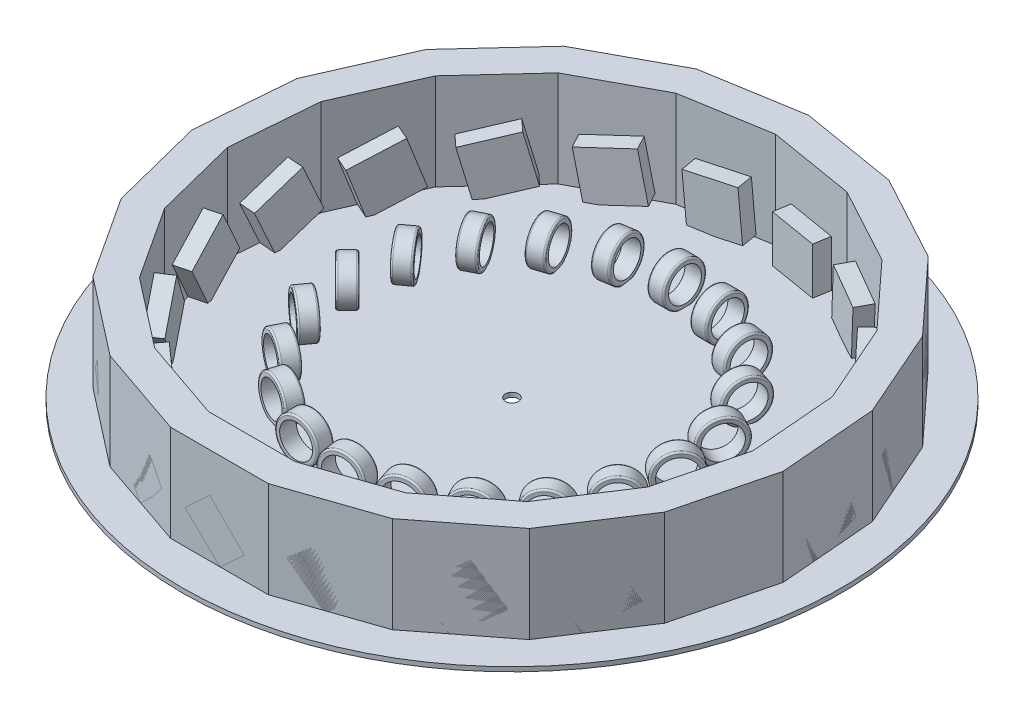
SolidWorks part; units mm, degrees
ref_plane "Front Plane" through (0, 0, 0) normal (0, 0, 1) x (1, 0, 0)
ref_plane "Top Plane" through (0, 0, 0) normal (0, 1, 0) x (1, 0, 0)
ref_plane "Right Plane" through (0, 0, 0) normal (1, 0, 0) x (0, 0, -1)
sketch "Sketch1" plane through (0, 0, 0) normal (0, 1, 0) x (1, 0, 0)
  circle A0 centre (0, 0) radius 100
  circle A1 centre (0, 0) radius 2
  dimension "D1" = 200
  dimension "D2" = 4
extrude "Base Platter" add sketch "Sketch1" along normal blind 0.75
sketch "Sketch3" plane through (0, 0.75, 0) normal (0, 1, 0) x (1, 0, 0)
  line L1 (0, 90) -> (-29.223, 85.1236)
  line L2 (-29.223, 85.1236) -> (-55.2791, 71.0226)
  line L3 (-55.2791, 71.0226) -> (-75.345, 49.2253)
  line L4 (-75.345, 49.2253) -> (-87.246, 22.0937)
  line L5 (-87.246, 22.0937) -> (-89.6926, -7.4321)
  line L6 (-89.6926, -7.4321) -> (-82.4196, -36.1526)
  line L7 (-82.4196, -36.1526) -> (-66.2152, -60.9553)
  line L8 (-66.2152, -60.9553) -> (-42.8353, -79.1526)
  line L9 (-42.8353, -79.1526) -> (-14.8135, -88.7725)
  line L10 (-14.8135, -88.7725) -> (14.8135, -88.7725)
  line L11 (14.8135, -88.7725) -> (42.8353, -79.1526)
  line L12 (42.8353, -79.1526) -> (66.2152, -60.9553)
  line L13 (66.2152, -60.9553) -> (82.4196, -36.1526)
  line L14 (82.4196, -36.1526) -> (89.6926, -7.4321)
  line L15 (89.6926, -7.4321) -> (87.246, 22.0937)
  line L16 (87.246, 22.0937) -> (75.345, 49.2253)
  line L17 (75.345, 49.2253) -> (55.2791, 71.0226)
  line L18 (55.2791, 71.0226) -> (29.223, 85.1236)
  line L19 (29.223, 85.1236) -> (0, 90)
  line L20 (0, 80) -> (-25.976, 75.6654)
  line L21 (-25.976, 75.6654) -> (-49.137, 63.1312)
  line L22 (-49.137, 63.1312) -> (-66.9733, 43.7559)
  line L23 (-66.9733, 43.7559) -> (-77.552, 19.6388)
  line L24 (-77.552, 19.6388) -> (-79.7268, -6.6063)
  line L25 (-79.7268, -6.6063) -> (-73.2619, -32.1356)
  line L26 (-73.2619, -32.1356) -> (-58.8579, -54.1825)
  line L27 (-58.8579, -54.1825) -> (-38.0758, -70.3579)
  line L28 (-38.0758, -70.3579) -> (-13.1676, -78.9089)
  line L29 (-13.1676, -78.9089) -> (13.1676, -78.9089)
  line L30 (13.1676, -78.9089) -> (38.0758, -70.3579)
  line L31 (38.0758, -70.3579) -> (58.8579, -54.1825)
  line L32 (58.8579, -54.1825) -> (73.2619, -32.1356)
  line L33 (73.2619, -32.1356) -> (79.7268, -6.6063)
  line L34 (79.7268, -6.6063) -> (77.552, 19.6388)
  line L35 (77.552, 19.6388) -> (66.9733, 43.7559)
  line L36 (66.9733, 43.7559) -> (49.137, 63.1312)
  line L37 (49.137, 63.1312) -> (25.976, 75.6654)
  line L38 (25.976, 75.6654) -> (0, 80)
  circle A0 centre (0, 0) radius 90 construction
  circle A1 centre (0, 0) radius 80 construction
  circle A2 centre (0, 0) radius 88.7725 construction
  circle A3 centre (0, 0) radius 78.9089 construction
  dimension "D1" = 180
  dimension "D2" = 160
extrude "Cube Face Reference" add sketch "Sketch3" along normal blind 29.8 separate body
sketch "Sketch4" plane through (14.6115, 0, -87.5618) normal (0.1646, 0, -0.9864) x (-0.9864, 0, -0.1646)
  line L0 (0, 0.75) -> (0, 30.55) construction
  line L1 (100, 0.75) -> (-100, 0.75) construction
  line L2 (-14.8135, 30.55) -> (14.8135, 30.55) construction
  line L3 (-14.8135, 0.75) -> (14.8135, 0.75) construction
  line L4 (-7.4075, 0.75) -> (7.4075, 0.75)
  line L5 (-7.4075, 0.75) -> (-7.4075, 15.57)
  line L6 (-7.4075, 15.57) -> (7.4075, 15.57)
  line L7 (7.4075, 0.75) -> (7.4075, 15.57)
  point P12 (0, 15.57)
  dimension "D1" = 14.815
  dimension "D2" = 14.82
extrude "First Cube" add sketch "Sketch4" against normal blind 14.82 separate body
sketch "Sketch5" plane through (42.251, 0, -78.0731) normal (0.4759, 0, -0.8795) x (-0.8795, 0, -0.4759)
  line L0 (-6.7728, 0.75) -> (7.9966, 1.9738)
  line L1 (-14.8135, 0.75) -> (14.8135, 0.75) construction
  line L2 (7.9966, 1.9738) -> (6.7728, 16.7432)
  line L3 (6.7728, 16.7432) -> (-7.9966, 15.5194)
  line L4 (-7.9966, 15.5194) -> (-6.7728, 0.75)
  line L5 (6.7728, 16.7432) -> (-6.7728, 0.75) construction
  line L6 (7.9966, 1.9738) -> (-7.9966, 15.5194) construction
  line L7 (100, 0.75) -> (-100, 0.75) construction
  line L8 (-14.8135, 30.55) -> (14.8135, 30.55) construction
  point P11 (0, 30.55)
  point P12 (0, 8.7466)
  dimension "D1" = 14.82
  dimension "D2" = 14.82
  dimension "D3" = 4.737
extrude "Boss-Extrude6" add sketch "Sketch5" against normal blind 14.82 separate body
sketch "Sketch6" plane through (65.3121, 0, -60.124) normal (0.7357, 0, -0.6773) x (-0.6773, 0, -0.7357)
  line L0 (-6.0893, 0.75) -> (-8.5286, 15.3679)
  line L1 (-14.8135, 0.75) -> (14.8135, 0.75) construction
  line L2 (-8.5286, 15.3679) -> (6.0893, 17.8072)
  line L3 (6.0893, 17.8072) -> (8.5286, 3.1893)
  line L4 (8.5286, 3.1893) -> (-6.0893, 0.75)
  line L5 (6.0893, 17.8072) -> (-6.0893, 0.75) construction
  line L6 (-8.5286, 15.3679) -> (8.5286, 3.1893) construction
  point P4 (0, 9.2786)
  dimension "D1" = 14.82
  dimension "D2" = 14.82
  dimension "D3" = 9.474
extrude "Boss-Extrude7" add sketch "Sketch6" against normal blind 14.82 separate body
sketch "Sketch7" plane through (81.2955, 0, -35.6595) normal (0.9158, 0, -0.4017) x (-0.4017, 0, -0.9158)
  line L0 (-5.3642, 0.75) -> (-9.0023, 15.1165)
  line L2 (-9.0023, 15.1165) -> (5.3642, 18.7546)
  line L3 (5.3642, 18.7546) -> (9.0023, 4.3881)
  line L4 (9.0023, 4.3881) -> (-5.3642, 0.75)
  line L5 (5.3642, 18.7546) -> (-5.3642, 0.75) construction
  line L6 (9.0023, 4.3881) -> (-9.0023, 15.1165) construction
  line L7 (100, 0.75) -> (-100, 0.75) construction
  line L8 (-14.8135, 0.75) -> (14.8135, 0.75) construction
  point P4 (0, 9.7523)
  dimension "D1" = 14.82
  dimension "D2" = 14.82
  dimension "D3" = 14.211
extrude "Boss-Extrude9" add sketch "Sketch7" against normal blind 14.82 separate body
sketch "Sketch8" plane through (88.4693, 0, -7.3308) normal (0.9966, 0, -0.0826) x (-0.0826, 0, -0.9966)
  line L0 (-4.6025, 0.75) -> (-9.4145, 14.767)
  line L2 (-9.4145, 14.767) -> (4.6025, 19.5791)
  line L3 (4.6025, 19.5791) -> (9.4145, 5.562)
  line L4 (9.4145, 5.562) -> (-4.6025, 0.75)
  line L5 (-14.8135, 0.75) -> (14.8135, 0.75) construction
  line L6 (-4.6025, 0.75) -> (4.6025, 19.5791) construction
  line L7 (9.4145, 5.562) -> (-9.4145, 14.767) construction
  line L8 (-14.8135, 30.55) -> (14.8135, 30.55) construction
  point P8 (0, 30.55)
  point P9 (0, 10.1645)
  dimension "D1" = 14.82
  dimension "D2" = 14.82
  dimension "D3" = 18.947
extrude "Boss-Extrude10" add sketch "Sketch8" against normal blind 14.82 separate body
sketch "Sketch9" plane through (86.0561, 0, 21.7924) normal (0.9694, 0, 0.2455) x (0.2455, 0, -0.9694)
  line L0 (-3.8093, 0.75) -> (-9.7624, 14.3218)
  line L1 (-14.8135, 0.75) -> (14.8135, 0.75) construction
  line L2 (-9.7624, 14.3218) -> (3.8093, 20.2749)
  line L3 (3.8093, 20.2749) -> (9.7624, 6.7031)
  line L4 (9.7624, 6.7031) -> (-3.8093, 0.75)
  line L5 (-3.8093, 0.75) -> (3.8093, 20.2749)
  line L6 (9.7624, 6.7031) -> (-9.7624, 14.3218)
  point P4 (0, 10.5124)
  dimension "D1" = 14.82
  dimension "D2" = 14.82
  dimension "D3" = 23.684
extrude "Boss-Extrude11" add sketch "Sketch9" against normal blind 14.82 separate body contours L6 L5 L2 | L6 L3 L5 | L4 L6 L5 | L5 L6 L0 region at (86.5432, 5.9885, 19.8687) region at (84.9455, 8.5281, 26.1779) region at (85.569, 15.0364, 23.716) region at (87.1667, 12.4968, 17.4069)
sketch "Sketch10" plane through (74.3174, 0, 48.554) normal (0.8372, 0, 0.5469) x (0.5469, 0, -0.8372)
  line L0 (-2.9901, 0.75) -> (-10.0437, 13.7838)
  line L1 (-14.8135, 0.75) -> (14.8135, 0.75) construction
  line L2 (-10.0437, 13.7838) -> (2.9901, 20.8373)
  line L3 (2.9901, 20.8373) -> (10.0437, 7.8035)
  line L4 (10.0437, 7.8035) -> (-2.9901, 0.75)
  line L5 (-2.9901, 0.75) -> (2.9901, 20.8373) construction
  line L6 (10.0437, 7.8035) -> (-10.0437, 13.7838) construction
  point P4 (0, 0.75)
  point P7 (0, 10.7937)
  dimension "D1" = 14.82
  dimension "D2" = 14.82
  dimension "D3" = 28.421
extrude "Boss-Extrude12" add sketch "Sketch10" against normal blind 14.82 separate body
sketch "Sketch11" plane through (54.5252, 0, 70.054) normal (0.6142, 0, 0.7891) x (0.7891, 0, -0.6142)
  line L0 (-2.1505, 0.75) -> (-10.2563, 13.1568)
  line L1 (-14.8135, 0.75) -> (14.8135, 0.75) construction
  line L2 (-10.2563, 13.1568) -> (2.1505, 21.2626)
  line L3 (2.1505, 21.2626) -> (10.2563, 8.8558)
  line L4 (10.2563, 8.8558) -> (-2.1505, 0.75)
  line L5 (2.1505, 21.2626) -> (-2.1505, 0.75) construction
  line L6 (10.2563, 8.8558) -> (-10.2563, 13.1568) construction
  line L7 (-14.8135, 30.55) -> (14.8135, 30.55) construction
  line L8 (100, 0.75) -> (-100, 0.75) construction
  point P8 (0, 30.55)
  point P9 (0, 11.0063)
  dimension "D1" = 14.82
  dimension "D2" = 14.82
  dimension "D3" = 33.158
extrude "Boss-Extrude14" add sketch "Sketch11" against normal blind 14.82 separate body
sketch "Sketch12" plane through (28.8244, 0, 83.9626) normal (0.3247, 0, 0.9458) x (0.9458, 0, -0.3247)
  line L0 (-1.2962, 0.75) -> (-10.3988, 12.4451)
  line L1 (100, 0.75) -> (-100, 0.75) construction
  line L2 (-10.3988, 12.4451) -> (1.2962, 21.5477)
  line L3 (1.2962, 21.5477) -> (10.3988, 9.8526)
  line L4 (10.3988, 9.8526) -> (-1.2962, 0.75)
  line L5 (1.2962, 21.5477) -> (-1.2962, 0.75) construction
  line L6 (-10.3988, 12.4451) -> (10.3988, 9.8526) construction
  line L7 (-14.8135, 30.55) -> (14.8135, 30.55) construction
  line L8 (-14.8135, 0.75) -> (14.8135, 0.75) construction
  point P8 (0, 30.55)
  point P9 (0, 11.1488)
  dimension "D1" = 14.82
  dimension "D2" = 14.82
  dimension "D3" = 37.895
extrude "Boss-Extrude15" add sketch "Sketch12" against normal blind 14.82 separate body
sketch "Sketch13" plane through (0, 0, 88.7725) normal (0, 0, 1) x (1, 0, 0)
  line L0 (-0.4331, 0.75) -> (-10.4704, 11.6534)
  line L1 (-14.8135, 0.75) -> (14.8135, 0.75) construction
  line L2 (-10.4704, 11.6534) -> (0.4331, 21.6907)
  line L3 (0.4331, 21.6907) -> (10.4704, 10.7873)
  line L4 (10.4704, 10.7873) -> (-0.4331, 0.75)
  line L5 (0.4331, 21.6907) -> (-0.4331, 0.75) construction
  line L6 (-10.4704, 11.6534) -> (10.4704, 10.7873) construction
  line L7 (100, 0.75) -> (-100, 0.75) construction
  point P8 (0, 0.75)
  point P9 (0, 11.2204)
  dimension "D1" = 14.82
  dimension "D2" = 14.82
  dimension "D3" = 42.632
extrude "Boss-Extrude16" add sketch "Sketch13" against normal blind 14.82 separate body
sketch "Sketch14" plane through (-28.8244, 0, 83.9626) normal (-0.3247, 0, 0.9458) x (0.9458, 0, 0.3247)
  line L0 (0.4331, 0.75) -> (-10.4704, 10.7873)
  line L1 (100, 0.75) -> (-100, 0.75) construction
  line L2 (-10.4704, 10.7873) -> (-0.4331, 21.6907)
  line L3 (-0.4331, 21.6907) -> (10.4704, 11.6534)
  line L4 (10.4704, 11.6534) -> (0.4331, 0.75)
  line L5 (0.4331, 0.75) -> (-0.4331, 21.6907) construction
  line L6 (-10.4704, 10.7873) -> (10.4704, 11.6534) construction
  line L7 (-14.8135, 0.75) -> (14.8135, 0.75) construction
  point P4 (0, 11.2204)
  dimension "D1" = 14.82
  dimension "D2" = 14.82
  dimension "D3" = 47.368
extrude "Boss-Extrude18" add sketch "Sketch14" against normal blind 14.82 separate body
sketch "Sketch15" plane through (-54.5252, 0, 70.054) normal (-0.6142, 0, 0.7891) x (0.7891, 0, 0.6142)
  line L0 (1.2962, 0.75) -> (-10.3988, 9.8526)
  line L1 (-14.8135, 0.75) -> (14.8135, 0.75) construction
  line L2 (-10.3988, 9.8526) -> (-1.2962, 21.5477)
  line L3 (-1.2962, 21.5477) -> (10.3988, 12.4451)
  line L4 (10.3988, 12.4451) -> (1.2962, 0.75)
  line L5 (1.2962, 0.75) -> (-1.2962, 21.5477) construction
  line L6 (10.3988, 12.4451) -> (-10.3988, 9.8526) construction
  line L7 (-14.8135, 30.55) -> (14.8135, 30.55) construction
  line L8 (100, 0.75) -> (-100, 0.75) construction
  point P8 (0, 30.55)
  point P9 (0, 11.1488)
  dimension "D1" = 14.82
  dimension "D2" = 14.82
  dimension "D3" = 52.105
extrude "Boss-Extrude19" add sketch "Sketch15" against normal blind 14.82 separate body
sketch "Sketch16" plane through (-74.3174, 0, 48.554) normal (-0.8372, 0, 0.5469) x (0.5469, 0, 0.8372)
  line L0 (2.1505, 0.75) -> (-10.2563, 8.8558)
  line L1 (-14.8135, 0.75) -> (14.8135, 0.75) construction
  line L2 (-10.2563, 8.8558) -> (-2.1505, 21.2626)
  line L3 (-2.1505, 21.2626) -> (10.2563, 13.1568)
  line L4 (10.2563, 13.1568) -> (2.1505, 0.75)
  line L5 (2.1505, 0.75) -> (-2.1505, 21.2626) construction
  line L6 (10.2563, 13.1568) -> (-10.2563, 8.8558) construction
  line L7 (-14.8135, 30.55) -> (14.8135, 30.55) construction
  point P8 (0, 30.55)
  point P9 (0, 11.0063)
  dimension "D1" = 14.82
  dimension "D2" = 14.82
  dimension "D3" = 56.842
extrude "Boss-Extrude20" add sketch "Sketch16" against normal blind 14.82 separate body
sketch "Sketch17" plane through (-86.0561, 0, 21.7924) normal (-0.9694, 0, 0.2455) x (0.2455, 0, 0.9694)
  line L0 (2.9901, 0.75) -> (-10.0437, 7.8035)
  line L1 (100, 0.75) -> (-100, 0.75) construction
  line L2 (-10.0437, 7.8035) -> (-2.9901, 20.8373)
  line L3 (-2.9901, 20.8373) -> (10.0437, 13.7838)
  line L4 (10.0437, 13.7838) -> (2.9901, 0.75)
  line L5 (2.9901, 0.75) -> (-2.9901, 20.8373) construction
  line L6 (10.0437, 13.7838) -> (-10.0437, 7.8035) construction
  line L7 (-14.8135, 30.55) -> (14.8135, 30.55) construction
  line L8 (-14.8135, 0.75) -> (14.8135, 0.75) construction
  point P8 (0, 30.55)
  point P9 (0, 10.7937)
  dimension "D1" = 14.82
  dimension "D2" = 14.82
  dimension "D3" = 14.82
  dimension "D4" = 61.579
extrude "Boss-Extrude21" add sketch "Sketch17" against normal blind 14.82 separate body
sketch "Sketch18" plane through (-88.4693, 0, -7.3308) normal (-0.9966, 0, -0.0826) x (-0.0826, 0, 0.9966)
  line L0 (3.8093, 0.75) -> (-9.7624, 6.7031)
  line L1 (100, 0.75) -> (-100, 0.75) construction
  line L2 (-9.7624, 6.7031) -> (-3.8093, 20.2749)
  line L3 (-3.8093, 20.2749) -> (9.7624, 14.3218)
  line L4 (9.7624, 14.3218) -> (3.8093, 0.75)
  line L5 (-3.8093, 20.2749) -> (3.8093, 0.75) construction
  line L6 (9.7624, 14.3218) -> (-9.7624, 6.7031) construction
  line L7 (-14.8135, 30.55) -> (14.8135, 30.55) construction
  line L8 (-14.8135, 0.75) -> (14.8135, 0.75) construction
  point P8 (0, 30.55)
  point P9 (0, 10.5124)
  dimension "D1" = 14.82
  dimension "D2" = 14.82
  dimension "D3" = 66.316
extrude "Boss-Extrude23" add sketch "Sketch18" against normal blind 14.82 separate body
sketch "Sketch19" plane through (-81.2955, 0, -35.6595) normal (-0.9158, 0, -0.4017) x (-0.4017, 0, 0.9158)
  line L0 (4.6025, 0.75) -> (-9.4145, 5.562)
  line L1 (-14.8135, 0.75) -> (14.8135, 0.75) construction
  line L2 (-9.4145, 5.562) -> (-4.6025, 19.5791)
  line L3 (-4.6025, 19.5791) -> (9.4145, 14.767)
  line L4 (9.4145, 14.767) -> (4.6025, 0.75)
  line L5 (4.6025, 0.75) -> (-4.6025, 19.5791) construction
  line L6 (9.4145, 14.767) -> (-9.4145, 5.562) construction
  line L7 (-14.8135, 30.55) -> (14.8135, 30.55) construction
  point P8 (0, 30.55)
  point P9 (0, 10.1645)
  dimension "D1" = 14.82
  dimension "D2" = 14.82
  dimension "D3" = 71.053
extrude "Boss-Extrude24" add sketch "Sketch19" against normal blind 14.82 separate body
sketch "Sketch20" plane through (-65.3121, 0, -60.124) normal (-0.7357, 0, -0.6773) x (-0.6773, 0, 0.7357)
  line L0 (5.3642, 0.75) -> (-9.0023, 4.3881)
  line L1 (100, 0.75) -> (-100, 0.75) construction
  line L2 (-9.0023, 4.3881) -> (-5.3642, 18.7546)
  line L3 (-5.3642, 18.7546) -> (9.0023, 15.1165)
  line L4 (9.0023, 15.1165) -> (5.3642, 0.75)
  line L5 (-5.3642, 18.7546) -> (5.3642, 0.75) construction
  line L6 (9.0023, 15.1165) -> (-9.0023, 4.3881) construction
  line L7 (-14.8135, 30.55) -> (14.8135, 30.55) construction
  point P8 (0, 30.55)
  point P9 (0, 9.7523)
  dimension "D1" = 14.82
  dimension "D2" = 14.82
  dimension "D3" = 75.789
extrude "Boss-Extrude25" add sketch "Sketch20" against normal blind 14.82 separate body
sketch "Sketch21" plane through (-42.251, 0, -78.0731) normal (-0.4759, 0, -0.8795) x (-0.8795, 0, 0.4759)
  line L0 (6.0893, 0.75) -> (-8.5286, 3.1893)
  line L1 (-14.8135, 0.75) -> (14.8135, 0.75) construction
  line L2 (-8.5286, 3.1893) -> (-6.0893, 17.8072)
  line L3 (-6.0893, 17.8072) -> (8.5286, 15.3679)
  line L4 (8.5286, 15.3679) -> (6.0893, 0.75)
  line L5 (6.0893, 0.75) -> (-6.0893, 17.8072) construction
  line L6 (8.5286, 15.3679) -> (-8.5286, 3.1893) construction
  line L7 (-14.8135, 30.55) -> (14.8135, 30.55) construction
  point P8 (0, 30.55)
  point P9 (0, 9.2786)
  dimension "D1" = 14.82
  dimension "D2" = 14.82
  dimension "D3" = 80.526
extrude "Boss-Extrude26" add sketch "Sketch21" against normal blind 14.82 separate body
sketch "Sketch22" plane through (-14.6115, 0, -87.5618) normal (-0.1646, 0, -0.9864) x (-0.9864, 0, 0.1646)
  line L0 (6.7728, 0.75) -> (-7.9966, 1.9738)
  line L1 (-14.8135, 0.75) -> (14.8135, 0.75) construction
  line L2 (-7.9966, 1.9738) -> (-6.7728, 16.7432)
  line L3 (-6.7728, 16.7432) -> (7.9966, 15.5194)
  line L4 (7.9966, 15.5194) -> (6.7728, 0.75)
  line L5 (6.7728, 0.75) -> (-6.7728, 16.7432) construction
  line L6 (-7.9966, 1.9738) -> (7.9966, 15.5194) construction
  line L7 (100, 0.75) -> (-100, 0.75) construction
  point P4 (0, 8.7466)
  dimension "D1" = 14.82
  dimension "D2" = 14.82
  dimension "D3" = 85.263
extrude "Boss-Extrude27" add sketch "Sketch22" against normal blind 14.82 separate body
sketch "Sketch23" plane through (0, 0.75, 0) normal (0, 1, 0) x (1, 0, 0)
  line L0 (0, 0) -> (0, 50) construction
  line L1 (0, 0) -> (15.4508, 47.5528) construction
  line L6 (0, 0) -> (29.3893, 40.4508) construction
  line L7 (0, 0) -> (40.4508, 29.3893) construction
  line L8 (0, 0) -> (47.5528, 15.4508) construction
  line L9 (0, 0) -> (50, 0) construction
  line L10 (0, 0) -> (47.5528, -15.4508) construction
  line L11 (0, 0) -> (40.4508, -29.3893) construction
  line L12 (0, 0) -> (29.3893, -40.4508) construction
  line L13 (0, 0) -> (15.4508, -47.5528) construction
  line L14 (0, 0) -> (0, -50) construction
  line L15 (0, 0) -> (-15.4508, -47.5528) construction
  line L16 (0, 0) -> (-29.3893, -40.4508) construction
  line L17 (0, 0) -> (-40.4508, -29.3893) construction
  line L18 (0, 0) -> (-47.5528, -15.4508) construction
  line L19 (0, 0) -> (-50, 0) construction
  line L20 (0, 0) -> (-47.5528, 15.4508) construction
  line L21 (0, 0) -> (-40.4508, 29.3893) construction
  line L22 (0, 0) -> (-29.3893, 40.4508) construction
  line L23 (0, 0) -> (-15.4508, 47.5528) construction
  line L24 (12.9508, 54.0528) -> (12.9508, 41.0528)
  line L25 (-2.5, 56.5) -> (2.5, 56.5)
  line L26 (-2.5, 56.5) -> (-2.5, 43.5)
  line L27 (-2.5, 43.5) -> (2.5, 43.5)
  line L28 (2.5, 56.5) -> (2.5, 43.5)
  line L29 (12.9508, 41.0528) -> (17.9508, 41.0528)
  line L30 (17.9508, 41.0528) -> (17.9508, 54.0528)
  line L31 (17.9508, 54.0528) -> (12.9508, 54.0528)
  line L32 (12.9508, 41.0528) -> (17.9508, 54.0528) construction
  line L33 (17.9508, 41.0528) -> (12.9508, 54.0528) construction
  line L34 (27.9369, 47.2619) -> (32.8753, 46.4797)
  line L35 (32.8753, 46.4797) -> (30.8417, 33.6398)
  line L36 (30.8417, 33.6398) -> (25.9032, 34.422)
  line L37 (25.9032, 34.422) -> (27.9369, 47.2619)
  line L38 (25.9032, 34.422) -> (32.8753, 46.4797) construction
  line L39 (30.8417, 33.6398) -> (27.9369, 47.2619) construction
  line L40 (40.0818, 36.3437) -> (36.0646, 23.9799)
  line L41 (36.0646, 23.9799) -> (40.8199, 22.4349)
  line L42 (40.8199, 22.4349) -> (44.8371, 34.7986)
  line L43 (44.8371, 34.7986) -> (40.0818, 36.3437)
  line L44 (40.8199, 22.4349) -> (40.0818, 36.3437) construction
  line L45 (44.8371, 34.7986) -> (36.0646, 23.9799) construction
  line L46 (48.2762, 22.3774) -> (42.3744, 10.7943)
  line L47 (42.3744, 10.7943) -> (46.8294, 8.5243)
  line L48 (46.8294, 8.5243) -> (52.7313, 20.1074)
  line L49 (52.7313, 20.1074) -> (48.2762, 22.3774)
  line L50 (46.8294, 8.5243) -> (48.2762, 22.3774) construction
  line L51 (52.7313, 20.1074) -> (42.3744, 10.7943) construction
  line L52 (51.7981, 6.7281) -> (44.1569, -3.7891)
  line L53 (44.1569, -3.7891) -> (48.2019, -6.7281)
  line L54 (48.2019, -6.7281) -> (55.8431, 3.7891)
  line L55 (55.8431, 3.7891) -> (51.7981, 6.7281)
  line L56 (48.2019, -6.7281) -> (51.7981, 6.7281) construction
  line L57 (55.8431, 3.7891) -> (44.1569, -3.7891) construction
  line L58 (50.3813, -9.0869) -> (41.1889, -18.2793)
  line L59 (41.1889, -18.2793) -> (44.7244, -21.8148)
  line L60 (44.7244, -21.8148) -> (53.9168, -12.6224)
  line L61 (53.9168, -12.6224) -> (50.3813, -9.0869)
  line L62 (44.7244, -21.8148) -> (50.3813, -9.0869) construction
  line L63 (53.9168, -12.6224) -> (41.1889, -18.2793) construction
  line L64 (44.24, -23.5461) -> (33.7228, -31.1873)
  line L65 (33.7228, -31.1873) -> (36.6617, -35.2324)
  line L66 (36.6617, -35.2324) -> (47.1789, -27.5912)
  line L67 (47.1789, -27.5912) -> (44.24, -23.5461)
  line L68 (36.6617, -35.2324) -> (44.24, -23.5461) construction
  line L69 (47.1789, -27.5912) -> (33.7228, -31.1873) construction
  line L70 (24.7327, -45.6293) -> (36.3158, -39.7274)
  line L71 (36.3158, -39.7274) -> (34.0458, -35.2724)
  line L72 (34.0458, -35.2724) -> (22.4627, -41.1743)
  line L73 (22.4627, -41.1743) -> (24.7327, -45.6293)
  line L74 (34.0458, -35.2724) -> (24.7327, -45.6293) construction
  line L75 (22.4627, -41.1743) -> (36.3158, -39.7274) construction
  line L76 (10.0415, -51.9391) -> (22.4053, -47.9219)
  line L77 (22.4053, -47.9219) -> (20.8602, -43.1666)
  line L78 (20.8602, -43.1666) -> (8.4964, -47.1838)
  line L79 (8.4964, -47.1838) -> (10.0415, -51.9391)
  line L80 (20.8602, -43.1666) -> (10.0415, -51.9391) construction
  line L81 (8.4964, -47.1838) -> (22.4053, -47.9219) construction
  line L82 (-6.0289, -53.486) -> (6.8111, -51.4524)
  line L83 (6.8111, -51.4524) -> (6.0289, -46.514)
  line L84 (6.0289, -46.514) -> (-6.8111, -48.5476)
  line L85 (-6.8111, -48.5476) -> (-6.0289, -53.486)
  line L86 (6.0289, -46.514) -> (-6.0289, -53.486) construction
  line L87 (-6.8111, -48.5476) -> (6.8111, -51.4524) construction
  line L88 (-21.9508, -50.0528) -> (-8.9508, -50.0528)
  line L89 (-8.9508, -50.0528) -> (-8.9508, -45.0528)
  line L90 (-8.9508, -45.0528) -> (-21.9508, -45.0528)
  line L91 (-21.9508, -45.0528) -> (-21.9508, -50.0528)
  line L92 (-8.9508, -45.0528) -> (-21.9508, -50.0528) construction
  line L93 (-21.9508, -45.0528) -> (-8.9508, -50.0528) construction
  line L94 (-36.3437, -40.8199) -> (-23.9799, -44.8371)
  line L95 (-23.9799, -44.8371) -> (-22.4349, -40.0818)
  line L96 (-22.4349, -40.0818) -> (-34.7986, -36.0646)
  line L97 (-34.7986, -36.0646) -> (-36.3437, -40.8199)
  line L98 (-22.4349, -40.0818) -> (-36.3437, -40.8199) construction
  line L99 (-34.7986, -36.0646) -> (-23.9799, -44.8371) construction
  line L100 (-47.3774, -28.6658) -> (-35.7943, -34.5677)
  line L101 (-35.7943, -34.5677) -> (-33.5243, -30.1127)
  line L102 (-33.5243, -30.1127) -> (-45.1074, -24.2108)
  line L103 (-45.1074, -24.2108) -> (-47.3774, -28.6658)
  line L104 (-33.5243, -30.1127) -> (-47.3774, -28.6658) construction
  line L105 (-45.1074, -24.2108) -> (-35.7943, -34.5677) construction
  line L106 (-54.2809, -13.6528) -> (-43.7637, -21.294)
  line L107 (-43.7637, -21.294) -> (-40.8248, -17.2489)
  line L108 (-40.8248, -17.2489) -> (-51.342, -9.6077)
  line L109 (-51.342, -9.6077) -> (-54.2809, -13.6528)
  line L110 (-40.8248, -17.2489) -> (-54.2809, -13.6528) construction
  line L111 (-51.342, -9.6077) -> (-43.7637, -21.294) construction
  line L112 (-56.364, 2.8284) -> (-47.1716, -6.364)
  line L113 (-47.1716, -6.364) -> (-43.636, -2.8284)
  line L114 (-43.636, -2.8284) -> (-52.8284, 6.364)
  line L115 (-52.8284, 6.364) -> (-56.364, 2.8284)
  line L116 (-43.636, -2.8284) -> (-56.364, 2.8284) construction
  line L117 (-52.8284, 6.364) -> (-47.1716, -6.364) construction
  line L118 (-53.396, 19.24) -> (-45.7548, 8.7228)
  line L119 (-45.7548, 8.7228) -> (-41.7097, 11.6617)
  line L120 (-41.7097, 11.6617) -> (-49.3509, 22.1789)
  line L121 (-49.3509, 22.1789) -> (-53.396, 19.24)
  line L122 (-41.7097, 11.6617) -> (-53.396, 19.24) construction
  line L123 (-49.3509, 22.1789) -> (-45.7548, 8.7228) construction
  line L124 (-45.6293, 34.0458) -> (-39.7274, 22.4627)
  line L125 (-39.7274, 22.4627) -> (-35.2724, 24.7327)
  line L126 (-35.2724, 24.7327) -> (-41.1743, 36.3158)
  line L127 (-41.1743, 36.3158) -> (-45.6293, 34.0458)
  line L128 (-35.2724, 24.7327) -> (-45.6293, 34.0458) construction
  line L129 (-41.1743, 36.3158) -> (-39.7274, 22.4627) construction
  line L130 (-33.7755, 45.8602) -> (-29.7583, 33.4964)
  line L131 (-29.7583, 33.4964) -> (-25.003, 35.0415)
  line L132 (-25.003, 35.0415) -> (-29.0202, 47.4053)
  line L133 (-29.0202, 47.4053) -> (-33.7755, 45.8602)
  line L134 (-25.003, 35.0415) -> (-33.7755, 45.8602) construction
  line L135 (-29.0202, 47.4053) -> (-29.7583, 33.4964) construction
  line L136 (-18.9369, 53.5817) -> (-16.9032, 40.7418)
  line L137 (-16.9032, 40.7418) -> (-11.9648, 41.5239)
  line L138 (-11.9648, 41.5239) -> (-13.9985, 54.3639)
  line L139 (-13.9985, 54.3639) -> (-18.9369, 53.5817)
  line L140 (-11.9648, 41.5239) -> (-18.9369, 53.5817) construction
  line L141 (-13.9985, 54.3639) -> (-16.9032, 40.7418) construction
  point P25 (0, 0)
  point P27 (0, 56.5)
  point P28 (2.5, 50)
  point P31 (15.4508, 47.5528)
  point P36 (29.3893, 40.4508)
  point P47 (-47.5528, -15.4508)
  point P50 (-50, 0)
  point P51 (-47.5528, 15.4508)
  point P54 (-40.4508, 29.3893)
  point P57 (-29.3893, 40.4508)
  point P63 (-15.4508, 47.5528)
  point P69 (29.3893, -40.4508)
  point P140 (40.4508, 29.3893)
  point P141 (47.5528, 15.4508)
  point P142 (50, 0)
  point P144 (47.5528, -15.4508)
  point P146 (40.4508, -29.3893)
  point P149 (15.4508, -47.5528)
  point P151 (0, -50)
  point P153 (-15.4508, -47.5528)
  point P154 (-29.3893, -40.4508)
  point P155 (-40.4508, -29.3893)
  dimension "D1" = 50
  dimension "D2" = 20
  dimension "D3" = 5
  dimension "D4" = 13
  dimension "D5" = 5
  dimension "D6" = 13
  dimension "D7" = 18
  dimension "D8" = 5
  dimension "D9" = 13
  dimension "D10" = 27
  dimension "D11" = 5
  dimension "D12" = 13
  dimension "D13" = 36
  dimension "D14" = 5
  dimension "D15" = 13
  dimension "D16" = 45
  dimension "D17" = 5
  dimension "D18" = 13
  dimension "D19" = 54
  dimension "D20" = 5
  dimension "D21" = 13
  dimension "D22" = 63
  dimension "D23" = 5
  dimension "D24" = 13
  dimension "D25" = 72
  dimension "D26" = 5
  dimension "D27" = 13
  dimension "D28" = 81
  dimension "D29" = 5
  dimension "D30" = 13
  dimension "D31" = 90
  dimension "D32" = 5
  dimension "D33" = 13
  dimension "D34" = 99
  dimension "D35" = 5
  dimension "D36" = 13
  dimension "D37" = 108
  dimension "D38" = 5
  dimension "D39" = 13
  dimension "D40" = 108
  dimension "D41" = 5
  dimension "D42" = 13
  dimension "D43" = 117
  dimension "D44" = 5
  dimension "D45" = 13
  dimension "D46" = 126
  dimension "D47" = 5
  dimension "D48" = 13
  dimension "D49" = 135
  dimension "D50" = 5
  dimension "D51" = 13
  dimension "D52" = 144
  dimension "D53" = 5
  dimension "D54" = 13
  dimension "D55" = 153
  dimension "D56" = 5
  dimension "D57" = 13
  dimension "D58" = 162
  dimension "D59" = 5
  dimension "D60" = 13
  dimension "D61" = 171
extrude "Rings" add sketch "Sketch23" along normal blind 13 separate body
sketch "Sketch26" plane through (-5.2562, 0, 0.8325) normal (0.9877, 0, -0.1564) x (-0.1564, 0, -0.9877)
  line L0 (42.8844, 13.75) -> (55.8844, 13.75) construction
  line L1 (55.8844, 13.75) -> (55.8844, 0.75) construction
  line L3 (42.8844, 13.75) -> (55.8844, 13.75)
  line L4 (42.8844, 13.75) -> (42.8844, 0.75)
  line L5 (42.8844, 0.75) -> (55.8844, 0.75)
  line L6 (55.8844, 13.75) -> (55.8844, 0.75)
  circle A0 centre (49.3844, 7.25) radius 5
  circle A1 centre (49.3844, 7.25) radius 6.5
  point P5 (49.3844, 13.75)
  point P8 (55.8844, 7.25)
  line M2 (42.8844, 0.75) -> (55.8844, 0.75)
  line M3 (55.8844, 0.75) -> (55.8844, 13.75)
  line M4 (55.8844, 13.75) -> (42.8844, 13.75)
  line M5 (42.8844, 13.75) -> (42.8844, 0.75)
  dimension "D1" = 10
  dimension "D2" = 13
extrude "Cut-Extrude2" cut sketch "Sketch26" against normal up to surface (5 mm away) contours A0 | A1 L3 M5 | A1 L6 M4 | A1 L5 M3 | A1 L4 M2 region at (-12.1919, 12.2981, -42.958) region at (-13.7713, 12.2981, -52.9299) region at (-12.1919, 2.2019, -42.958) region at (-13.7713, 2.2019, -52.9299) region at (-12.9816, 7.25, -47.9439) up to face at (-17.9201, 7.25, -47.1617)
sketch "Sketch27" plane through (2.5, 0, 0) normal (1, 0, 0) x (0, 0, -1)
  line L0 (43.5, 13.75) -> (56.5, 13.75) construction
  line L1 (56.5, 13.75) -> (56.5, 0.75) construction
  line L3 (43.5, 13.75) -> (56.5, 13.75)
  line L4 (43.5, 13.75) -> (43.5, 0.75)
  line L5 (43.5, 0.75) -> (56.5, 0.75)
  line L6 (56.5, 13.75) -> (56.5, 0.75)
  circle A0 centre (50, 7.25) radius 5
  circle A1 centre (50, 7.25) radius 6.5
  point P4 (50, 13.75)
  point P7 (56.5, 7.25)
  line M2 (43.5, 0.75) -> (56.5, 0.75)
  line M3 (56.5, 0.75) -> (56.5, 13.75)
  line M4 (56.5, 13.75) -> (43.5, 13.75)
  line M5 (43.5, 13.75) -> (43.5, 0.75)
  dimension "D1" = 10
  dimension "D2" = 13
extrude "Cut-Extrude3" cut sketch "Sketch27" against normal up to surface (5 mm away) contours A0 | A1 L3 M5 | A1 L4 M2 | A1 L6 M4 | A1 L5 M3 region at (2.5, 12.2981, -44.9519) region at (2.5, 12.2981, -55.0481) region at (2.5, 2.2019, -44.9519) region at (2.5, 2.2019, -55.0481) region at (2.5, 7.25, -50) up to face at (-2.5, 7.25, -50)
sketch "Sketch28" plane through (17.9508, 0, 0) normal (1, 0, 0) x (0, 0, -1)
  line L0 (41.0528, 13.75) -> (54.0528, 13.75) construction
  line L1 (54.0528, 13.75) -> (54.0528, 0.75) construction
  line L3 (41.0528, 13.75) -> (54.0528, 13.75)
  line L4 (41.0528, 13.75) -> (41.0528, 0.75)
  line L5 (41.0528, 0.75) -> (54.0528, 0.75)
  line L6 (54.0528, 13.75) -> (54.0528, 0.75)
  circle A0 centre (47.5528, 7.25) radius 5
  circle A1 centre (47.5528, 7.25) radius 6.5
  point P4 (47.5528, 13.75)
  point P7 (54.0528, 7.25)
  line M2 (41.0528, 0.75) -> (54.0528, 0.75)
  line M3 (54.0528, 0.75) -> (54.0528, 13.75)
  line M4 (54.0528, 13.75) -> (41.0528, 13.75)
  line M5 (41.0528, 13.75) -> (41.0528, 0.75)
  dimension "D1" = 10
  dimension "D2" = 13
extrude "Cut-Extrude4" cut sketch "Sketch28" against normal up to surface (5 mm away) contours A1 L3 M5 | A1 L4 M2 | A0 | A1 L6 M4 | A1 L5 M3 region at (17.9508, 12.2981, -42.5047) region at (17.9508, 12.2981, -52.6009) region at (17.9508, 2.2019, -42.5047) region at (17.9508, 2.2019, -52.6009) region at (17.9508, 7.25, -47.5528) up to face at (12.9508, 7.25, -47.5528)
sketch "Sketch29" plane through (24.8893, 0, 3.9421) normal (0.9877, 0, 0.1564) x (0.1564, 0, -0.9877)
  line L0 (38.0503, 13.75) -> (51.0503, 13.75) construction
  line L1 (51.0503, 13.75) -> (51.0503, 0.75) construction
  line L3 (38.0503, 13.75) -> (51.0503, 13.75)
  line L4 (38.0503, 13.75) -> (38.0503, 0.75)
  line L5 (38.0503, 0.75) -> (51.0503, 0.75)
  line L6 (51.0503, 13.75) -> (51.0503, 0.75)
  circle A0 centre (44.5503, 7.25) radius 5
  circle A1 centre (44.5503, 7.25) radius 6.5
  point P4 (44.5503, 13.75)
  point P7 (51.0503, 7.25)
  line M2 (38.0503, 0.75) -> (51.0503, 0.75)
  line M3 (51.0503, 0.75) -> (51.0503, 13.75)
  line M4 (51.0503, 13.75) -> (38.0503, 13.75)
  line M5 (38.0503, 13.75) -> (38.0503, 0.75)
  dimension "D1" = 10
  dimension "D2" = 13
extrude "Cut-Extrude5" cut sketch "Sketch29" against normal up to surface (5 mm away) contours A0 | A1 L3 M5 | A1 L4 M2 | A1 L5 M3 | A1 L6 M4 region at (31.0688, 12.2981, -35.0738) region at (32.6482, 12.2981, -45.0457) region at (31.0688, 2.2019, -35.0738) region at (32.6482, 2.2019, -45.0457) region at (31.8585, 7.25, -40.0598) up to face at (26.92, 7.25, -40.8419)
sketch "Sketch30" plane through (30.3285, 0, 9.8543) normal (0.9511, 0, 0.309) x (0.309, 0, -0.9511)
  line L0 (33.9508, 13.75) -> (46.9508, 13.75) construction
  line L1 (46.9508, 13.75) -> (46.9508, 0.75) construction
  line L3 (33.9508, 13.75) -> (46.9508, 13.75)
  line L4 (33.9508, 13.75) -> (33.9508, 0.75)
  line L5 (33.9508, 0.75) -> (46.9508, 0.75)
  line L6 (46.9508, 13.75) -> (46.9508, 0.75)
  circle A0 centre (40.4508, 7.25) radius 5
  circle A1 centre (40.4508, 7.25) radius 6.5
  point P4 (40.4508, 13.75)
  point P7 (46.9508, 7.25)
  line M2 (33.9508, 0.75) -> (46.9508, 0.75)
  line M3 (46.9508, 0.75) -> (46.9508, 13.75)
  line M4 (46.9508, 13.75) -> (33.9508, 13.75)
  line M5 (33.9508, 13.75) -> (33.9508, 0.75)
  dimension "D1" = 10
  dimension "D2" = 13
extrude "Cut-Extrude6" cut sketch "Sketch30" against normal up to surface (5 mm away) contours A1 L3 M5 | A1 L4 M2 | A0 | A1 L6 M4 | A1 L5 M3 region at (41.2685, 12.2981, -23.8157) region at (44.3884, 12.2981, -33.4178) region at (41.2685, 2.2019, -23.8157) region at (44.3884, 2.2019, -33.4178) region at (42.8285, 7.25, -28.6167) up to face at (38.0732, 7.25, -30.1618)
sketch "Sketch31" plane through (33.7294, 0, 17.186) normal (0.891, 0, 0.454) x (0.454, 0, -0.891)
  line L0 (28.8553, 13.75) -> (41.8553, 13.75) construction
  line L1 (41.8553, 13.75) -> (41.8553, 0.75) construction
  line L3 (28.8553, 13.75) -> (41.8553, 13.75)
  line L4 (28.8553, 13.75) -> (28.8553, 0.75)
  line L5 (28.8553, 0.75) -> (41.8553, 0.75)
  line L6 (41.8553, 13.75) -> (41.8553, 0.75)
  circle A0 centre (35.3553, 7.25) radius 5
  circle A1 centre (35.3553, 7.25) radius 6.5
  point P4 (35.3553, 13.75)
  point P7 (41.8553, 7.25)
  line M2 (28.8553, 0.75) -> (41.8553, 0.75)
  line M3 (41.8553, 0.75) -> (41.8553, 13.75)
  line M4 (41.8553, 13.75) -> (28.8553, 13.75)
  line M5 (28.8553, 13.75) -> (28.8553, 0.75)
  dimension "D1" = 10
  dimension "D2" = 13
extrude "Cut-Extrude7" cut sketch "Sketch31" against normal up to surface (5 mm away) contours A1 L3 M5 | A1 L4 M2 | A0 | A1 L6 M4 | A1 L5 M3 region at (47.4885, 12.2981, -9.818) region at (52.0721, 12.2981, -18.8138) region at (47.4885, 2.2019, -9.818) region at (52.0721, 2.2019, -18.8138) region at (49.7803, 7.25, -14.3159) up to face at (45.3253, 7.25, -16.5858)
sketch "Sketch32" plane through (34.748, 0, 25.2459) normal (0.809, 0, 0.5878) x (0.5878, 0, -0.809)
  line L0 (22.8893, 13.75) -> (35.8893, 13.75) construction
  line L1 (35.8893, 13.75) -> (35.8893, 0.75) construction
  line L3 (22.8893, 13.75) -> (35.8893, 13.75)
  line L4 (22.8893, 13.75) -> (22.8893, 0.75)
  line L5 (22.8893, 0.75) -> (35.8893, 0.75)
  line L6 (35.8893, 13.75) -> (35.8893, 0.75)
  circle A0 centre (29.3893, 7.25) radius 5
  circle A1 centre (29.3893, 7.25) radius 6.5
  point P5 (29.3893, 13.75)
  point P8 (35.8893, 7.25)
  line M2 (22.8893, 0.75) -> (35.8893, 0.75)
  line M3 (35.8893, 0.75) -> (35.8893, 13.75)
  line M4 (35.8893, 13.75) -> (22.8893, 13.75)
  line M5 (22.8893, 13.75) -> (22.8893, 0.75)
  dimension "D1" = 10
  dimension "D2" = 13
extrude "Cut-Extrude8" cut sketch "Sketch32" against normal up to surface (5 mm away) contours A1 L3 M5 | A1 L4 M2 | A0 | A1 L6 M4 | A1 L5 M3 region at (49.0553, 12.2981, 5.5535) region at (54.9897, 12.2981, -2.6145) region at (49.0553, 2.2019, 5.5535) region at (54.9897, 2.2019, -2.6145) region at (52.0225, 7.25, 1.4695) up to face at (47.9775, 7.25, -1.4695)
sketch "Sketch33" plane through (33.2696, 0, 33.2696) normal (0.7071, 0, 0.7071) x (0.7071, 0, -0.7071)
  line L0 (16.1995, 13.75) -> (29.1995, 13.75) construction
  line L1 (29.1995, 13.75) -> (29.1995, 0.75) construction
  line L3 (16.1995, 13.75) -> (29.1995, 13.75)
  line L4 (16.1995, 13.75) -> (16.1995, 0.75)
  line L5 (16.1995, 0.75) -> (29.1995, 0.75)
  line L6 (29.1995, 13.75) -> (29.1995, 0.75)
  circle A0 centre (22.6995, 7.25) radius 5
  circle A1 centre (22.6995, 7.25) radius 6.5
  point P4 (22.6995, 13.75)
  point P7 (29.1995, 7.25)
  line M2 (16.1995, 0.75) -> (29.1995, 0.75)
  line M3 (29.1995, 0.75) -> (29.1995, 13.75)
  line M4 (29.1995, 13.75) -> (16.1995, 13.75)
  line M5 (16.1995, 13.75) -> (16.1995, 0.75)
  dimension "D1" = 10
  dimension "D2" = 13
extrude "Cut-Extrude9" cut sketch "Sketch33" against normal up to surface (5 mm away) contours A1 L3 M5 | A1 L4 M2 | A0 | A1 L6 M4 | A1 L5 M3 region at (45.751, 12.2981, 20.7882) region at (52.8901, 12.2981, 13.6491) region at (45.751, 2.2019, 20.7882) region at (52.8901, 2.2019, 13.6491) region at (49.3206, 7.25, 17.2186) up to face at (45.7851, 7.25, 13.6831)
sketch "Sketch34" plane through (29.4203, 0, 40.4936) normal (0.5878, 0, 0.809) x (0.809, 0, -0.5878)
  line L0 (8.9508, 13.75) -> (21.9508, 13.75) construction
  line L1 (21.9508, 13.75) -> (21.9508, 0.75) construction
  line L3 (8.9508, 13.75) -> (21.9508, 13.75)
  line L4 (8.9508, 13.75) -> (8.9508, 0.75)
  line L5 (8.9508, 0.75) -> (21.9508, 0.75)
  line L6 (21.9508, 13.75) -> (21.9508, 0.75)
  circle A0 centre (15.4508, 7.25) radius 5
  circle A1 centre (15.4508, 7.25) radius 6.5
  point P4 (15.4508, 13.75)
  point P7 (21.9508, 7.25)
  line M2 (8.9508, 0.75) -> (21.9508, 0.75)
  line M3 (21.9508, 0.75) -> (21.9508, 13.75)
  line M4 (21.9508, 13.75) -> (8.9508, 13.75)
  line M5 (8.9508, 13.75) -> (8.9508, 0.75)
  dimension "D1" = 10
  dimension "D2" = 13
extrude "Cut-Extrude10" cut sketch "Sketch34" against normal up to surface (5 mm away) contours A1 L4 M2 | A1 L3 M5 | A0 | A1 L6 M4 | A1 L5 M3 region at (37.8363, 12.2981, 34.379) region at (46.0043, 12.2981, 28.4446) region at (37.8363, 2.2019, 34.379) region at (46.0043, 2.2019, 28.4446) region at (41.9203, 7.25, 31.4118) up to face at (38.9814, 7.25, 27.3667)
sketch "Sketch35" plane through (23.555, 0, 46.2294) normal (0.454, 0, 0.891) x (0.891, 0, -0.454)
  line L0 (1.3217, 13.75) -> (14.3217, 13.75) construction
  line L1 (14.3217, 13.75) -> (14.3217, 0.75) construction
  line L3 (1.3217, 13.75) -> (14.3217, 13.75)
  line L4 (1.3217, 13.75) -> (1.3217, 0.75)
  line L5 (1.3217, 0.75) -> (14.3217, 0.75)
  line L6 (14.3217, 13.75) -> (14.3217, 0.75)
  circle A0 centre (7.8217, 7.25) radius 5
  circle A1 centre (7.8217, 7.25) radius 6.5
  point P4 (7.8217, 13.75)
  point P7 (14.3217, 7.25)
  line M2 (1.3217, 0.75) -> (14.3217, 0.75)
  line M3 (14.3217, 0.75) -> (14.3217, 13.75)
  line M4 (14.3217, 13.75) -> (1.3217, 13.75)
  line M5 (1.3217, 13.75) -> (1.3217, 0.75)
  dimension "D1" = 10
  dimension "D2" = 13
extrude "Cut-Extrude11" cut sketch "Sketch35" against normal up to surface (5 mm away) contours A1 L4 M2 | A1 L3 M5 | A0 | A1 L6 M4 | A1 L5 M3 region at (26.0263, 12.2981, 44.9702) region at (35.0221, 12.2981, 40.3866) region at (26.0263, 2.2019, 44.9702) region at (35.0221, 2.2019, 40.3866) region at (30.5242, 7.25, 42.6784) up to face at (28.2543, 7.25, 38.2233)
sketch "Sketch36" plane through (16.2234, 0, 49.9305) normal (0.309, 0, 0.9511) x (0.9511, 0, -0.309)
  line L0 (-6.5, 13.75) -> (6.5, 13.75) construction
  line L1 (6.5, 13.75) -> (6.5, 0.75) construction
  line L3 (-6.5, 13.75) -> (6.5, 13.75)
  line L4 (-6.5, 13.75) -> (-6.5, 0.75)
  line L5 (-6.5, 0.75) -> (6.5, 0.75)
  line L6 (6.5, 13.75) -> (6.5, 0.75)
  circle A0 centre (0, 7.25) radius 5
  circle A1 centre (0, 7.25) radius 6.5
  point P4 (0, 13.75)
  point P7 (6.5, 7.25)
  line M2 (-6.5, 0.75) -> (6.5, 0.75)
  line M3 (6.5, 0.75) -> (6.5, 13.75)
  line M4 (6.5, 13.75) -> (-6.5, 13.75)
  line M5 (-6.5, 13.75) -> (-6.5, 0.75)
  dimension "D1" = 10
  dimension "D2" = 13
extrude "Cut-Extrude12" cut sketch "Sketch36" against normal up to surface (5 mm away) contours A1 L3 M5 | A1 L4 M2 | A0 | A1 L5 M3 | A1 L6 M4 region at (11.4224, 12.2981, 51.4904) region at (21.0244, 12.2981, 48.3705) region at (11.4224, 2.2019, 51.4904) region at (21.0244, 2.2019, 48.3705) region at (16.2234, 7.25, 49.9305) up to face at (14.6783, 7.25, 45.1752)
sketch "Sketch37" plane through (8.1165, 0, 51.2456) normal (0.1564, 0, 0.9877) x (0.9877, 0, -0.1564)
  line L0 (-14.3217, 13.75) -> (-1.3217, 13.75) construction
  line L1 (-1.3217, 13.75) -> (-1.3217, 0.75) construction
  line L3 (-1.3217, 0.75) -> (-14.3217, 0.75)
  line L4 (-1.3217, 0.75) -> (-1.3217, 13.75)
  line L5 (-1.3217, 13.75) -> (-14.3217, 13.75)
  line L6 (-14.3217, 0.75) -> (-14.3217, 13.75)
  circle A0 centre (-7.8217, 7.25) radius 5
  circle A1 centre (-7.8217, 7.25) radius 6.5
  point P4 (-7.8217, 13.75)
  point P7 (-1.3217, 7.25)
  line M2 (-14.3217, 0.75) -> (-1.3217, 0.75)
  line M3 (-1.3217, 0.75) -> (-1.3217, 13.75)
  line M4 (-1.3217, 13.75) -> (-14.3217, 13.75)
  line M5 (-14.3217, 13.75) -> (-14.3217, 0.75)
  dimension "D1" = 10
  dimension "D2" = 13
extrude "Cut-Extrude13" cut sketch "Sketch37" against normal up to surface (5 mm away) contours A1 L5 M5 | A1 L6 M2 | A0 | A1 L4 M4 | A1 L3 M3 region at (5.377, 2.2019, 51.6795) region at (-4.5949, 2.2019, 53.2589) region at (5.377, 12.2981, 51.6795) region at (-4.5949, 12.2981, 53.2589) region at (0.3911, 7.25, 52.4692) up to face at (-0.3911, 7.25, 47.5308)
sketch "Sketch38" plane through (0, 0, 50.0528) normal (0, 0, 1) x (1, 0, 0)
  line L0 (-21.9508, 13.75) -> (-8.9508, 13.75) construction
  line L1 (-8.9508, 13.75) -> (-8.9508, 0.75) construction
  line L3 (-21.9508, 13.75) -> (-8.9508, 13.75)
  line L4 (-21.9508, 13.75) -> (-21.9508, 0.75)
  line L5 (-21.9508, 0.75) -> (-8.9508, 0.75)
  line L6 (-8.9508, 13.75) -> (-8.9508, 0.75)
  circle A0 centre (-15.4508, 7.25) radius 5
  circle A1 centre (-15.4508, 7.25) radius 6.5
  point P4 (-15.4508, 13.75)
  point P7 (-8.9508, 7.25)
  line M2 (-21.9508, 0.75) -> (-8.9508, 0.75)
  line M3 (-8.9508, 0.75) -> (-8.9508, 13.75)
  line M4 (-8.9508, 13.75) -> (-21.9508, 13.75)
  line M5 (-21.9508, 13.75) -> (-21.9508, 0.75)
  dimension "D1" = 10
  dimension "D2" = 13
extrude "Cut-Extrude14" cut sketch "Sketch38" against normal up to surface (5 mm away) contours A1 L3 M5 | A1 L4 M2 | A0 | A1 L6 M4 | A1 L5 M3 region at (-20.499, 12.2981, 50.0528) region at (-10.4027, 12.2981, 50.0528) region at (-20.499, 2.2019, 50.0528) region at (-10.4027, 2.2019, 50.0528) region at (-15.4508, 7.25, 50.0528) up to face at (-15.4508, 7.25, 45.0528)
sketch "Sketch39" plane through (-15.4672, 0, 47.6031) normal (-0.309, 0, 0.9511) x (0.9511, 0, 0.309)
  line L0 (-21.9508, 13.75) -> (-8.9508, 13.75) construction
  line L1 (-8.9508, 13.75) -> (-8.9508, 0.75) construction
  line L3 (-21.9508, 13.75) -> (-8.9508, 13.75)
  line L4 (-21.9508, 13.75) -> (-21.9508, 0.75)
  line L5 (-21.9508, 0.75) -> (-8.9508, 0.75)
  line L6 (-8.9508, 13.75) -> (-8.9508, 0.75)
  circle A0 centre (-15.4508, 7.25) radius 5
  circle A1 centre (-15.4508, 7.25) radius 6.5
  point P4 (-15.4508, 13.75)
  point P7 (-8.9508, 7.25)
  line M2 (-21.9508, 0.75) -> (-8.9508, 0.75)
  line M3 (-8.9508, 0.75) -> (-8.9508, 13.75)
  line M4 (-8.9508, 13.75) -> (-21.9508, 13.75)
  line M5 (-21.9508, 13.75) -> (-21.9508, 0.75)
  dimension "D1" = 10
  dimension "D2" = 13
extrude "Cut-Extrude15" cut sketch "Sketch39" against normal up to surface (5 mm away) contours A1 L3 M5 | A1 L4 M2 | A1 L6 M4 | A0 | A1 L5 M3 region at (-34.9628, 12.2981, 41.2685) region at (-25.3608, 12.2981, 44.3884) region at (-34.9628, 2.2019, 41.2685) region at (-25.3608, 2.2019, 44.3884) region at (-30.1618, 7.25, 42.8285) up to face at (-28.6167, 7.25, 38.0732)
sketch "Sketch40" plane through (-21.3604, 0, 41.9221) normal (-0.454, 0, 0.891) x (0.891, 0, 0.454)
  line L0 (-29.1995, 13.75) -> (-16.1995, 13.75) construction
  line L1 (-16.1995, 13.75) -> (-16.1995, 0.75) construction
  line L3 (-29.1995, 13.75) -> (-16.1995, 13.75)
  line L4 (-29.1995, 13.75) -> (-29.1995, 0.75)
  line L5 (-29.1995, 0.75) -> (-16.1995, 0.75)
  line L6 (-16.1995, 13.75) -> (-16.1995, 0.75)
  circle A0 centre (-22.6995, 7.25) radius 5
  circle A1 centre (-22.6995, 7.25) radius 6.5
  point P4 (-22.6995, 13.75)
  point P7 (-16.1995, 7.25)
  line M2 (-29.1995, 0.75) -> (-16.1995, 0.75)
  line M3 (-16.1995, 0.75) -> (-16.1995, 13.75)
  line M4 (-16.1995, 13.75) -> (-29.1995, 13.75)
  line M5 (-29.1995, 13.75) -> (-29.1995, 0.75)
  dimension "D1" = 10
  dimension "D2" = 13
extrude "Cut-Extrude16" cut sketch "Sketch40" against normal up to surface (5 mm away) contours A1 L3 M5 | A1 L6 M4 | A0 | A1 L5 M3 | A1 L4 M2 region at (-46.0837, 12.2981, 29.325) region at (-37.0879, 12.2981, 33.9086) region at (-46.0837, 2.2019, 29.325) region at (-37.0879, 2.2019, 33.9086) region at (-41.5858, 7.25, 31.6168) up to face at (-39.3159, 7.25, 27.1617)
sketch "Sketch41" plane through (-25.2459, 0, 34.748) normal (-0.5878, 0, 0.809) x (0.809, 0, 0.5878)
  line L0 (-35.8893, 13.75) -> (-22.8893, 13.75) construction
  line L1 (-35.8893, 13.75) -> (-35.8893, 0.75) construction
  line L3 (-35.8893, 13.75) -> (-22.8893, 13.75)
  line L4 (-35.8893, 13.75) -> (-35.8893, 0.75)
  line L5 (-35.8893, 0.75) -> (-22.8893, 0.75)
  line L6 (-22.8893, 13.75) -> (-22.8893, 0.75)
  circle A0 centre (-29.3893, 7.25) radius 5
  circle A1 centre (-29.3893, 7.25) radius 6.5
  point P4 (-29.3893, 13.75)
  point P7 (-35.8893, 7.25)
  line M2 (-35.8893, 0.75) -> (-22.8893, 0.75)
  line M3 (-22.8893, 0.75) -> (-22.8893, 13.75)
  line M4 (-22.8893, 13.75) -> (-35.8893, 13.75)
  line M5 (-35.8893, 13.75) -> (-35.8893, 0.75)
  dimension "D1" = 10
  dimension "D2" = 13
extrude "Cut-Extrude17" cut sketch "Sketch41" against normal up to surface (5 mm away) contours A1 L6 M4 | A1 L3 M5 | A0 | A1 L5 M3 | A1 L4 M2 region at (-53.1063, 12.2981, 14.5062) region at (-44.9383, 12.2981, 20.4406) region at (-53.1063, 2.2019, 14.5062) region at (-44.9383, 2.2019, 20.4406) region at (-49.0223, 7.25, 17.4734) up to face at (-46.0834, 7.25, 13.4283)
sketch "Sketch42" plane through (-26.7678, 0, 26.7678) normal (-0.7071, 0, 0.7071) x (0.7071, 0, 0.7071)
  line L0 (-41.8553, 13.75) -> (-28.8553, 13.75) construction
  line L1 (-28.8553, 13.75) -> (-28.8553, 0.75) construction
  line L3 (-41.8553, 13.75) -> (-28.8553, 13.75)
  line L4 (-41.8553, 13.75) -> (-41.8553, 0.75)
  line L5 (-41.8553, 0.75) -> (-28.8553, 0.75)
  line L6 (-28.8553, 13.75) -> (-28.8553, 0.75)
  circle A0 centre (-35.3553, 7.25) radius 5
  circle A1 centre (-35.3553, 7.25) radius 6.5
  point P4 (-35.3553, 13.75)
  point P7 (-28.8553, 7.25)
  line M2 (-41.8553, 0.75) -> (-28.8553, 0.75)
  line M3 (-28.8553, 0.75) -> (-28.8553, 13.75)
  line M4 (-28.8553, 13.75) -> (-41.8553, 13.75)
  line M5 (-41.8553, 13.75) -> (-41.8553, 0.75)
  dimension "D1" = 10
  dimension "D2" = 13
extrude "Cut-Extrude18" cut sketch "Sketch42" against normal up to surface (5 mm away) contours A1 L3 M5 | A1 L6 M4 | A0 | A1 L5 M3 | A1 L4 M2 region at (-55.3373, 12.2981, -1.8018) region at (-48.1982, 12.2981, 5.3373) region at (-55.3373, 2.2019, -1.8018) region at (-48.1982, 2.2019, 5.3373) region at (-51.7678, 7.25, 1.7678) up to face at (-48.2322, 7.25, -1.7678)
sketch "Sketch43" plane through (-25.799, 0, 18.744) normal (-0.809, 0, 0.5878) x (0.5878, 0, 0.809)
  line L0 (-46.9508, 13.75) -> (-33.9508, 13.75) construction
  line L1 (-46.9508, 13.75) -> (-46.9508, 0.75) construction
  line L3 (-46.9508, 13.75) -> (-33.9508, 13.75)
  line L4 (-46.9508, 13.75) -> (-46.9508, 0.75)
  line L5 (-46.9508, 0.75) -> (-33.9508, 0.75)
  line L6 (-33.9508, 13.75) -> (-33.9508, 0.75)
  circle A0 centre (-40.4508, 7.25) radius 5
  circle A1 centre (-40.4508, 7.25) radius 6.5
  point P4 (-40.4508, 13.75)
  point P7 (-46.9508, 7.25)
  line M2 (-46.9508, 0.75) -> (-33.9508, 0.75)
  line M3 (-33.9508, 0.75) -> (-33.9508, 13.75)
  line M4 (-33.9508, 13.75) -> (-46.9508, 13.75)
  line M5 (-46.9508, 13.75) -> (-46.9508, 0.75)
  dimension "D1" = 10
  dimension "D2" = 13
extrude "Cut-Extrude19" cut sketch "Sketch43" against normal up to surface (5 mm away) contours A1 L5 M3 | A1 L6 M4 | A0 | A1 L3 M5 | A1 L4 M2 region at (-52.5426, 12.2981, -18.0654) region at (-46.6082, 12.2981, -9.8974) region at (-52.5426, 2.2019, -18.0654) region at (-46.6082, 2.2019, -9.8974) region at (-49.5754, 7.25, -13.9814) up to face at (-45.5303, 7.25, -16.9203)
sketch "Sketch44" plane through (-22.4529, 0, 11.4403) normal (-0.891, 0, 0.454) x (0.454, 0, 0.891)
  line L0 (-51.0503, 13.75) -> (-38.0503, 13.75) construction
  line L1 (-51.0503, 13.75) -> (-51.0503, 0.75) construction
  line L3 (-51.0503, 13.75) -> (-38.0503, 13.75)
  line L4 (-51.0503, 13.75) -> (-51.0503, 0.75)
  line L5 (-51.0503, 0.75) -> (-38.0503, 0.75)
  line L6 (-38.0503, 13.75) -> (-38.0503, 0.75)
  circle A0 centre (-44.5503, 7.25) radius 5
  circle A1 centre (-44.5503, 7.25) radius 6.5
  point P4 (-44.5503, 13.75)
  point P7 (-51.0503, 7.25)
  line M2 (-51.0503, 0.75) -> (-38.0503, 0.75)
  line M3 (-38.0503, 0.75) -> (-38.0503, 13.75)
  line M4 (-38.0503, 13.75) -> (-51.0503, 13.75)
  line M5 (-51.0503, 13.75) -> (-51.0503, 0.75)
  dimension "D1" = 10
  dimension "D2" = 13
extrude "Cut-Extrude20" cut sketch "Sketch44" against normal up to surface (5 mm away) contours A1 L4 M2 | A1 L5 M3 | A1 L6 M4 | A0 | A1 L3 M5 region at (-44.9702, 12.2981, -32.7522) region at (-40.3866, 12.2981, -23.7564) region at (-44.9702, 2.2019, -32.7522) region at (-40.3866, 2.2019, -23.7564) region at (-42.6784, 7.25, -28.2543) up to face at (-38.2233, 7.25, -30.5242)
sketch "Sketch45" plane through (-17.0723, 0, 5.5471) normal (-0.9511, 0, 0.309) x (0.309, 0, 0.9511)
  line L0 (-54.0528, 13.75) -> (-41.0528, 13.75) construction
  line L1 (-54.0528, 13.75) -> (-54.0528, 0.75) construction
  line L3 (-54.0528, 13.75) -> (-41.0528, 13.75)
  line L4 (-54.0528, 13.75) -> (-54.0528, 0.75)
  line L5 (-54.0528, 0.75) -> (-41.0528, 0.75)
  line L6 (-41.0528, 13.75) -> (-41.0528, 0.75)
  circle A0 centre (-47.5528, 7.25) radius 5
  circle A1 centre (-47.5528, 7.25) radius 6.5
  point P4 (-47.5528, 13.75)
  point P7 (-54.0528, 7.25)
  line M2 (-54.0528, 0.75) -> (-41.0528, 0.75)
  line M3 (-41.0528, 0.75) -> (-41.0528, 13.75)
  line M4 (-41.0528, 13.75) -> (-54.0528, 13.75)
  line M5 (-54.0528, 13.75) -> (-54.0528, 0.75)
  dimension "D1" = 10
  dimension "D2" = 13
extrude "Cut-Extrude21" cut sketch "Sketch45" against normal up to surface (5 mm away) contours A1 L5 M3 | A1 L4 M2 | A0 | A1 L6 M4 | A1 L3 M5 region at (-33.3269, 12.2981, -44.4793) region at (-30.207, 12.2981, -34.8773) region at (-33.3269, 2.2019, -44.4793) region at (-30.207, 2.2019, -34.8773) region at (-31.7669, 7.25, -39.6783) up to face at (-27.0116, 7.25, -41.2234)
sketch "Sketch46" plane through (0, 0.75, 0) normal (0, 1, 0) x (1, 0, 0)
  circle A0 centre (0, 0) radius 100
  circle A1 centre (0, 0) radius 2
extrude "Boss-Extrude29" add sketch "Sketch46" along normal blind 0.6
fillet "Fillet1" radius 0.5 40 edges at (-46.0834, 13.75, 13.4283) (-49.0223, 13.75, 17.4734) (-41.5858, 13.75, 31.6168) (-39.3159, 13.75, 27.1617) (-28.6167, 13.75, 38.0732) (-30.1618, 13.75, 42.8285) (-15.4508, 13.75, 50.0528) (-15.4508, 13.75, 45.0528) (-0.3911, 13.75, 47.5308) (0.3911, 13.75, 52.4692) (16.2234, 13.75, 49.9305) (14.6783, 13.75, 45.1752) (28.2543, 13.75, 38.2233) (30.5242, 13.75, 42.6784) (41.9203, 13.75, 31.4118) (38.9814, 13.75, 27.3667) (45.7851, 13.75, 13.6831) (49.3206, 13.75, 17.2186) (52.0225, 13.75, 1.4695) (47.9775, 13.75, -1.4695) (49.7803, 13.75, -14.3159) (45.3253, 13.75, -16.5858) (42.8285, 13.75, -28.6167) (38.0732, 13.75, -30.1618) (31.8585, 13.75, -40.0598) (26.92, 13.75, -40.8419) (17.9508, 13.75, -47.5528) (12.9508, 13.75, -47.5528) (2.5, 13.75, -50) (-2.5, 13.75, -50) (-12.9816, 13.75, -47.9439) (-17.9201, 13.75, -47.1617) (-27.0116, 13.75, -41.2234) (-31.7669, 13.75, -39.6783) (-38.2233, 13.75, -30.5242) (-42.6784, 13.75, -28.2543) (-45.5303, 13.75, -16.9203) (-49.5754, 13.75, -13.9814) (-48.2322, 13.75, -1.7678) (-51.7678, 13.75, 1.7678)
